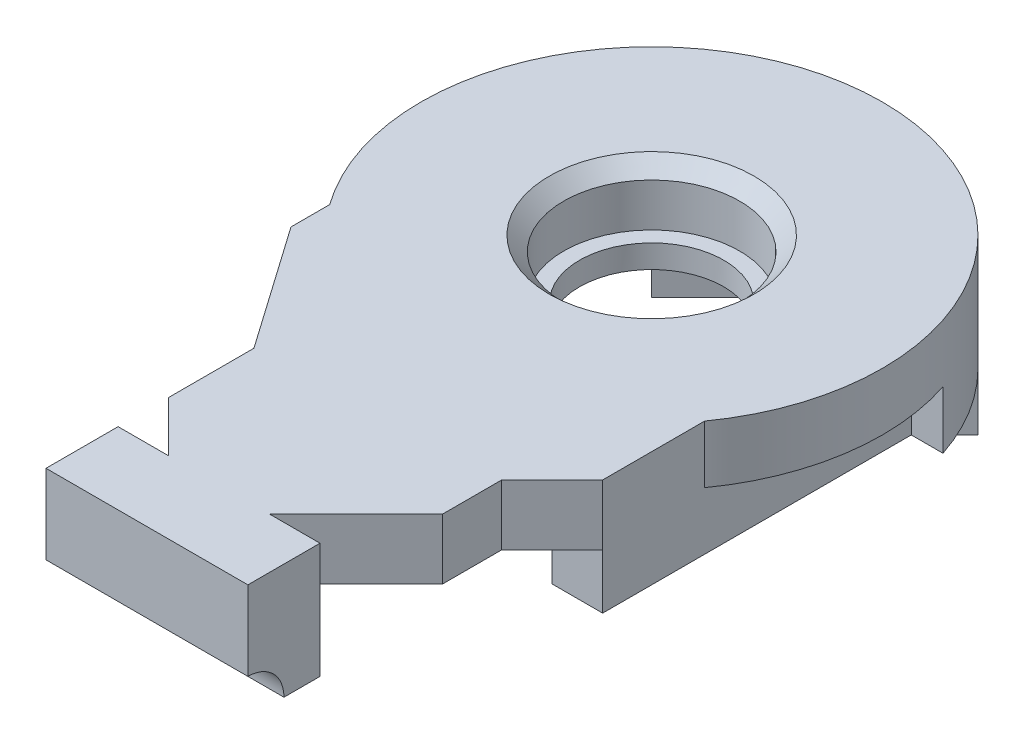
SolidWorks part; units mm, degrees
other "Markup1"
sketch "Sketch13" plane through (-8, -6, 20) normal (-0.3378, -0.0842, 0.9374) x (-0.8101, -0.4811, -0.3351)
ref_plane "Front Plane" through (0, 0, 0) normal (0, 0, 1) x (1, 0, 0)
ref_plane "Top Plane" through (0, 0, 0) normal (0, 1, 0) x (1, 0, 0)
ref_plane "Right Plane" through (0, 0, 0) normal (1, 0, 0) x (0, 0, -1)
sketch "Sketch1" plane through (0, 0, 0) normal (0, 1, 0) x (1, 0, 0)
  line L0 (-996.0269, -20) -> (49003.9731, -20) construction
  line L3 (-6.5, -20) -> (6.5, -20)
  line L4 (6.5, -1010) -> (6.5, -4.6637) construction
  line L5 (-6.5, -1010) -> (-6.5, -4.6637) construction
  line L6 (6.5, -4.6637) -> (6.5, -20)
  line L7 (-6.5, -4.6637) -> (-6.5, -20)
  line L8 (-6.5, 4.6637) -> (-6.5, 48990) construction
  line L9 (6.5, 4.6637) -> (6.5, 48990) construction
  arc A0 (6.5, 4.6637) -> (-6.5, 4.6637) centre (0, 0) ccw
  arc A1 (-8, 0) -> (8, 0) centre (0, 0) ccw construction
  arc A2 (-6.5, 4.6637) -> (-8, 0) centre (0, 0) ccw construction
  arc A3 (8, 0) -> (6.5, 4.6637) centre (0, 0) ccw construction
  arc A4 (-6.5, 4.6637) -> (-6.5, -4.6637) centre (0, 0) ccw
  arc A5 (6.5, 4.6637) -> (6.5, -4.6637) centre (0, 0) cw
  dimension "D1" = 16
  dimension "D2" = 20
  dimension "D3" = 6.5
  dimension "D4" = 6.5
extrude "Boss-Extrude1" add sketch "Sketch1" against normal blind 4
sketch "Sketch2" plane through (0, 0, 0) normal (0, 1, 0) x (1, 0, 0)
  circle A1 centre (0, 0) radius 2.5
  dimension "D1" = 5
extrude "Cut-Extrude1" cut sketch "Sketch2" against normal through all
sketch "Sketch3" plane through (0, 0, 0) normal (0, 1, 0) x (1, 0, 0)
  circle A0 centre (0, 0) radius 3.05
  dimension "D1" = 6.1
extrude "Cut-Extrude2" cut sketch "Sketch3" against normal blind 2
sketch "Sketch4" plane through (0, -4, 0) normal (0, -1, 0) x (1, 0, 0)
  line L0 (0, 0) -> (0, -5.75) construction
  line L1 (2.5, -5.75) -> (-2.5, -5.75)
  line L2 (5.75, 0) -> (-5.75, 0) construction
  line L3 (5.75, -1000) -> (5.75, 49000) construction
  line L4 (-5.75, -1000) -> (-5.75, 49000) construction
  line L5 (2.5, -5.75) -> (5.75, -2.5)
  line L6 (5.75, -2.5) -> (5.75, 6.75)
  line L7 (-2.5, -5.75) -> (-5.75, -2.5)
  line L8 (-5.75, -2.5) -> (-5.75, 6.75)
  line L9 (-999.8306, 8.2) -> (49000.1694, 8.2) construction
  line L10 (2.9, 8.2) -> (2.1, 8.2) construction
  line L12 (-5.75, 6.75) -> (-4.75, 6.75)
  line L13 (-5.5, 6.5) -> (5.5, 6.5) construction
  line L14 (-4.75, 6.75) -> (-4.75, 8.2)
  line L15 (-6.5, 20) -> (6.5, 20) construction
  line L16 (-2.9, 6.8941) -> (-2.9, 8.2) construction
  line L17 (4.75, 6.75) -> (4.75, 8.2)
  line L18 (-6.5, 20) -> (6.5, 20) construction
  line L19 (2.9, 6.8941) -> (2.9, 8.2) construction
  line L21 (-4.75, 6.75) -> (4.75, 6.75) construction
  line L22 (4.75, 6.75) -> (5.75, 6.75)
  line L23 (4.75, 8.2) -> (6.0104, 10) construction
  line L24 (-4.75, 8.2) -> (-6.0104, 10)
  line L25 (4.75, 8.2) -> (4.75, 20) construction
  line L26 (-4.75, 8.2) -> (-4.75, 20) construction
  line L27 (6.5, 10.6993) -> (6.5, 15)
  line L31 (-6.5, 10.6993) -> (-6.5, 15)
  line L33 (-6.5, 15) -> (-6.5, 20.6628) construction
  line L34 (-1005.75, -2.5) -> (48994.25, -2.5) construction
  line L35 (-999.9505, 10) -> (49000.0495, 10) construction
  line L36 (6.5, 10.6993) -> (6.5, 10)
  line L37 (-6.5, 15) -> (6.5, 15)
  line L39 (6.5, 15) -> (6.5, 20.6628) construction
  line L40 (6.5, 20) -> (6.5, 4.6637) construction
  line L41 (6.5, 10) -> (6.0104, 10) construction
  line L42 (5.75, 9.6281) -> (6.5, 10.6993) construction
  line L43 (6.0104, 10) -> (5.75, 9.6281) construction
  line L44 (-6.5, 10.6993) -> (-6.5, 10)
  line L45 (-6.5, 4.6637) -> (-6.5, 20) construction
  line L46 (-6.5, 10) -> (-6.0104, 10)
  line L47 (-6.0104, 10) -> (-5.75, 9.6281) construction
  line L48 (-5.75, 9.6281) -> (-6.5, 10.6993) construction
  line L49 (4.75, 8.2) -> (6.5, 8.2)
  line L50 (6.5, 8.2) -> (6.5, 10)
  point P6 (0, -5.75)
  point P9 (0, 0)
  dimension "D3" = 0.25
  dimension "D1" = 5.75
  dimension "D2" = 11.5
  dimension "D4" = 1.85
  dimension "D5" = 1.85
  dimension "D6" = 2.5
  dimension "D7" = 10
  dimension "D8" = 15
  dimension "D9" = 6.75
  dimension "D10" = 35
  dimension "D11" = 35
extrude "Cut-Extrude3" cut sketch "Sketch4" against normal blind 1.2
sketch "Sketch6" plane through (0, -2.8, 0) normal (0, -1, 0) x (1, 0, 0)
  line L0 (6.5, 15) -> (6.5, 8.2)
  line L2 (4.75, 8.2) -> (4.75, 6.2)
  line L3 (4.75, 6.2) -> (-4.75, 6.2)
  line L5 (6.5, 15) -> (-6.5, 15)
  line L6 (-6.5, 15) -> (-6.5, 10.6993)
  line L7 (-6.0104, 10) -> (-4.75, 8.2)
  line L8 (-4.75, 8.2) -> (-4.75, 6.2)
  line L12 (6.5, 8.2) -> (6.5, 15) construction
  line L13 (6.5, 8.2) -> (4.75, 8.2)
  line L15 (-6.0104, 10) -> (-4.75, 8.2) construction
  line L16 (-6.5, 10.6993) -> (-6.5, 10)
  line L17 (-6.5, 15) -> (-6.5, 10) construction
  line L18 (-6.5, 10) -> (-6.0104, 10)
  line L19 (-6.5, 10) -> (-6.0104, 10) construction
  line L20 (-6.5, 10.6993) -> (-6.0104, 10) construction
  line L21 (4.75, 8.2) -> (6.5, 8.2) construction
  dimension "D1" = 2
extrude "Cut-Extrude5" cut sketch "Sketch6" against normal blind 0.7
sketch "Sketch7" plane through (0, 0, 20) normal (0, 0, 1) x (1, 0, 0)
  line L1 (-6.5, -4) -> (6.5, -4)
  line L2 (-6.5, -4) -> (-6.5, 0)
  line L3 (-6.5, 0) -> (6.5, 0)
  line L4 (6.5, -4) -> (6.5, 0)
extrude "Cut-Extrude6" [suppressed] cut sketch "Sketch7" against normal up to vertex
sketch "Sketch10" plane through (0, -4, 0) normal (0, -1, 0) x (1, 0, 0)
  line L0 (-6.5, 4.6637) -> (-6.5, -2.5)
  line L1 (6.5, 4.6637) -> (6.5, -2.5)
  line L2 (-1005.75, -2.5) -> (48994.25, -2.5) construction
  line L3 (-6.5, -2.5) -> (-7.5993, -2.5)
  line L4 (-6.5, -2.5) -> (-6.5, -4.6637) construction
  line L5 (6.5, -2.5) -> (7.5993, -2.5)
  line L6 (6.5, -2.5) -> (6.5, -4.6637) construction
  arc A0 (-6.5, 4.6637) -> (6.5, 4.6637) centre (0, 0) ccw construction
  arc A1 (-6.5, 4.6637) -> (-7.5993, -2.5) centre (0, 0) ccw
  arc A2 (6.5, 4.6637) -> (7.5993, -2.5) centre (0, 0) cw
  arc A3 (-7.5993, -2.5) -> (-6.5, -4.6637) centre (0, 0) ccw construction
  arc A4 (7.5993, -2.5) -> (6.5, -4.6637) centre (0, 0) cw construction
  dimension "D1" = 8
  dimension "D2" = 8
extrude "Cut-Extrude8" cut sketch "Sketch10" against normal blind 2
sketch "Sketch11" plane through (0, -4, 0) normal (0, -1, 0) x (1, 0, 0)
  line L0 (0, -1000) -> (0, 49000) construction
  line L1 (-0.75, -1003.313) -> (-0.75, 48996.687) construction
  line L2 (0.75, -1004.6428) -> (0.75, 48995.3572) construction
  line L3 (-0.75, -7.9648) -> (-0.75, -5.75)
  line L4 (-0.75, -5.75) -> (-2.5, -5.75)
  line L6 (0.75, -7.9648) -> (0.75, -5.75)
  line L7 (0.75, -5.75) -> (2.5, -5.75)
  line L9 (-2.5, -5.75) -> (2.5, -5.75) construction
  line L10 (0, 0) -> (35355.3391, -35355.3391) construction
  line L11 (2.5, -5.75) -> (5.75, -2.5) construction
  line L12 (0, 0) -> (-35355.3391, -35355.3391) construction
  line L13 (-5.75, -2.5) -> (-2.5, -5.75) construction
  line L14 (-2.5, -5.75) -> (-4.125, -4.125)
  line L15 (-4.125, -4.125) -> (-5.6569, -5.6569)
  line L16 (2.5, -5.75) -> (4.125, -4.125)
  line L17 (4.125, -4.125) -> (5.6569, -5.6569)
  arc A0 (-7.5993, -2.5) -> (7.5993, -2.5) centre (0, 0) ccw construction
  arc A1 (-5.6569, -5.6569) -> (-0.75, -7.9648) centre (0, 0) ccw
  arc A2 (5.6569, -5.6569) -> (0.75, -7.9648) centre (0, 0) cw
  point P27 (4.125, -4.125)
  point P32 (-4.125, -4.125)
  dimension "D1" = 0.75
  dimension "D2" = 0.75
extrude "Boss-Extrude3" add sketch "Sketch11" along normal blind 2
sketch "Sketch12" plane through (0, -4, 0) normal (0, -1, 0) x (1, 0, 0)
  line L0 (0, 20) -> (0, 15) construction
  line L1 (-6.5, 20) -> (6.5, 20) construction
  line L2 (6.5, 15) -> (-6.5, 15) construction
  line L3 (1.5, 15) -> (1.5, 20)
  line L4 (-1.5, 15) -> (-1.5, 20)
  line L5 (-1.5, 20) -> (1.5, 20)
  line L7 (1.5, 15) -> (-1.5, 15)
  line L8 (1.5, 15) -> (0, 15) construction
  dimension "D1" = 1.5
  dimension "D2" = 1.5
extrude "Cut-Extrude9" [suppressed] cut sketch "Sketch12" against normal up to surface (1.9 mm away)
sketch "Sketch14" plane through (0, -2.1, 0) normal (0, -1, 0) x (1, 0, 0)
  line L0 (-4.75, 8.2) -> (-6.0104, 10)
  line L1 (-6.0104, 10) -> (-6.5, 10)
  line L2 (-6.5, 10) -> (-6.5, 15)
  line L3 (-6.5, 15) -> (-4.75, 15)
  line L4 (6.5, 15) -> (-6.5, 15) construction
  line L5 (-4.75, 15) -> (-4.75, 8.2)
  line L6 (-6.5, 10) -> (-6.0104, 10) construction
extrude "Boss-Extrude4" add sketch "Sketch14" along normal up to surface (1.9 mm away) up to face at (-5.7577, -4, 2.4304)
sketch "Sketch15" plane through (0, -4, 0) normal (0, -1, 0) x (1, 0, 0)
  line L0 (4.75, 8.2) -> (-6.5, 8.2) construction
  line L1 (-6.5, 4.6637) -> (-6.5, 20) construction
  line L2 (-4.75, 15) -> (-6.5, 15) construction
  line L3 (-6.5, 15) -> (-6.5, 8.2)
  line L4 (-6.5, 8.2) -> (-4.75, 8.2)
  line L5 (-4.75, 15) -> (-4.75, 6.2) construction
  line L6 (-4.75, 8.2) -> (-4.75, 15)
  line L7 (-6.5, 20) -> (6.5, 20) construction
  line L8 (-4.75, 15) -> (-3.5, 15)
  line L9 (-6.5, 15) -> (-6.5, 20)
  line L10 (-6.5, 20) -> (-3.5, 20)
  line L11 (-3.5, 15) -> (-3.5, 20)
  line L12 (-6.5, 15) -> (-4.75, 15) construction
  line L13 (0, -3.3) -> (0, 3.3) construction
  line L14 (6.5, 8.2) -> (4.75, 8.2)
  line L15 (6.5, 15) -> (6.5, 8.2)
  line L16 (6.5, 15) -> (6.5, 20)
  line L17 (6.5, 20) -> (3.5, 20)
  line L18 (3.5, 15) -> (3.5, 20)
  line L19 (4.75, 15) -> (3.5, 15)
  line L20 (4.75, 8.2) -> (4.75, 15)
  dimension "D1" = 3
extrude "Cut-Extrude10" cut sketch "Sketch15" against normal through all both and the other way through all
sketch "Sketch16" plane through (0, 0, 0) normal (0, 1, 0) x (1, 0, 0)
  line L0 (-4.75, -12) -> (-1.75, -15)
  line L1 (3.5, -15) -> (-3.5, -15) construction
  line L2 (-1.75, -15) -> (-4.75, -15)
  line L3 (-4.75, -15) -> (-3.5, -15) construction
  line L4 (-4.75, -8.2) -> (-4.75, -15) construction
  line L5 (-1.75, -15) -> (-4.75, -15)
  line L6 (-4.75, -12) -> (-4.75, -15)
  line L7 (4.75, -15) -> (1.75, -15)
  line L9 (1.75, -15) -> (4.75, -12)
  line L10 (4.75, -12) -> (4.75, -15)
  line L12 (4.75, -15) -> (4.75, -8.2) construction
  dimension "D1" = 45
  dimension "D2" = 3
  dimension "D3" = 3
  dimension "D4" = 45
extrude "Cut-Extrude11" cut sketch "Sketch16" against normal through all
sketch "Sketch17" plane through (3.5, 0, 0) normal (1, 0, 0) x (0, 0, -1)
  line L0 (-15, -4) -> (-20, -4) construction
  line L1 (-16.25, -4) -> (-18.75, -4)
  arc A0 (-16.25, -4) -> (-18.75, -4) centre (-17.5, -4) ccw
  arc A1 (-18.75, -4) -> (-16.25, -4) centre (-17.5, -4) ccw construction
  dimension "D1" = 2.5
extrude "Cut-Extrude12" cut sketch "Sketch17" against normal through all both and the other way through all
chamfer "Chamfer1" distance 1.75 angle 45 2 edges at (-4.75, -1.05, 8.2) (4.75, -1.05, 8.2)
sketch "Sketch18" plane through (3.5, 0, 0) normal (1, 0, 0) x (0, 0, -1)
  line L1 (-18.75, -4) -> (-20, -4)
  line L2 (-18.75, -4) -> (-18.75, 0) construction
  line L3 (-18.75, 0) -> (-20, 0)
  line L4 (-20, -4) -> (-20, 0)
  line L5 (-17.5, -2.75) -> (-18.75, -2.75) construction
  line L6 (-17.5, -2.75) -> (-17.5, 0)
  line L7 (-17.5, 0) -> (-18.75, 0)
  line L8 (-18.75, -2.75) -> (-18.75, 0) construction
  arc A0 (-16.25, -4) -> (-18.75, -4) centre (-17.5, -4) ccw construction
  arc A1 (-18.75, -4) -> (-17.5, -2.75) centre (-17.5, -4) cw
extrude "Cut-Extrude13" cut sketch "Sketch18" against normal through all
sketch "Sketch19" plane through (0, 0, 0) normal (0, 1, 0) x (1, 0, 0)
  line L0 (-3.5, -10.2905) -> (-6.5, -6.006)
  line L1 (-3.5, -10.2905) -> (-3.5, -13.25)
  line L2 (-6.5, -6.006) -> (-6.5, -13.25)
  line L3 (-3.5, -15) -> (-3.5, -17.5) construction
  line L4 (-4.75, -12) -> (-1.75, -15) construction
  line L5 (-6.5, -4.6637) -> (-6.5, -8.2) construction
  line L6 (-3.5, -13.25) -> (-6.5, -13.25)
  dimension "D1" = 35
  dimension "D2" = 8.85
extrude "Cut-Extrude14" cut sketch "Sketch19" against normal through all
sketch "Sketch20" [suppressed] plane through (0, -2.1, 0) normal (0, -1, 0) x (1, 0, 0)
  line L3 (-4.75, 9.95) -> (-4.75, 8.2)
  line L4 (-4.75, 8.2) -> (-6.5, 8.2)
  line L5 (-6.5, 8.2) -> (-4.75, 9.95)
extrude "Boss-Extrude5" [suppressed] add sketch "Sketch20" along normal up to surface (1.9 mm away)
chamfer "Chamfer2" distance 0.5 angle 45 1 edges at (0, 0, 3.05)
